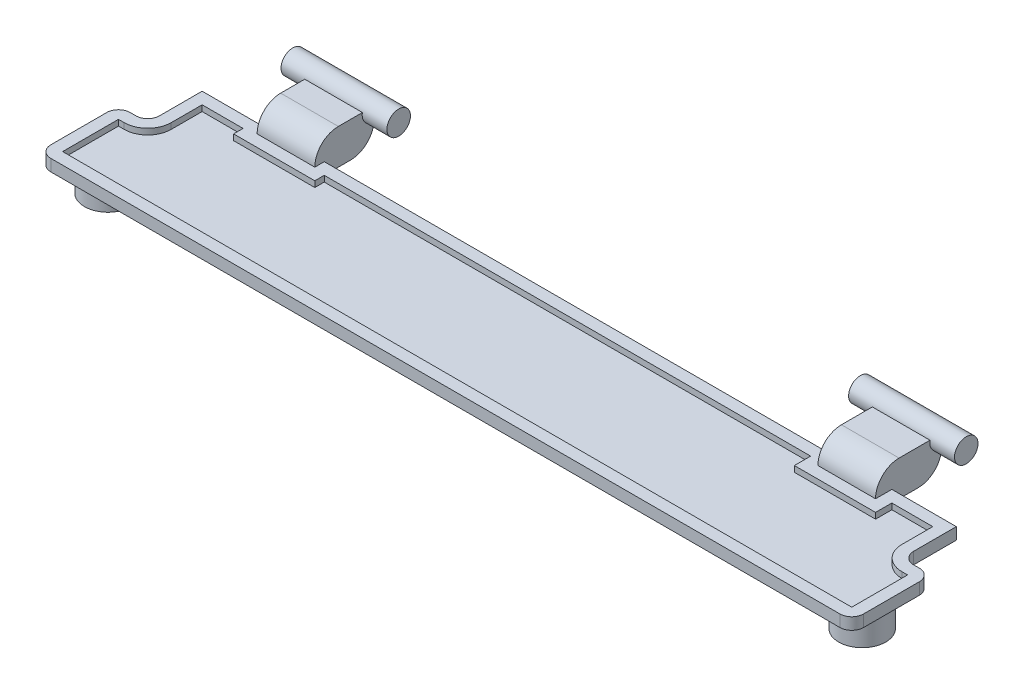
SolidWorks part; units mm, degrees
material "Alloy Steel"
ref_plane "Front Plane" through (0, 0, 0) normal (0, 0, 1) x (1, 0, 0)
ref_plane "Top Plane" through (0, 0, 0) normal (0, 1, 0) x (1, 0, 0)
ref_plane "Right Plane" through (0, 0, 0) normal (1, 0, 0) x (0, 0, -1)
sketch "Sketch1" plane through (0, 0, 0) normal (0, 1, 0) x (1, 0, 0)
  line L0 (0, 0) -> (64.1, 0) construction
  circle A0 centre (64.1, 0) radius 2
  circle A1 centre (0, 0) radius 2
extrude "Boss-Extrude1" add sketch "Sketch1" along normal blind 2.5
sketch "Sketch2" plane through (0, 2.5, 0) normal (0, 1, 0) x (1, 0, 0)
  line L3 (0, 3.3731) -> (0, 8)
  line L4 (0, 8) -> (64.1, 8)
  line L5 (64.1, 3.3731) -> (64.1, 8)
  line L6 (66.5854, -3.3731) -> (-2.4854, -3.3731)
  line L7 (66.5854, -3.3731) -> (66.5854, 3.3731)
  line L8 (66.5854, 3.3731) -> (64.1, 3.3731)
  line L9 (-2.4854, -3.3731) -> (-2.4854, 3.3731)
  line L12 (0, 3.3731) -> (-2.4854, 3.3731)
  point P4 (32.05, 0)
  point P7 (32.05, 0)
extrude "Boss-Extrude3" add sketch "Sketch2" along normal blind 1
fillet "Fillet1" radius 1 6 edges at (0, 3, -3.3731) (64.1, 3, -3.3731) (66.5854, 3, -3.3731) (66.5854, 3, 3.3731) (-2.4854, 3, 3.3731) (-2.4854, 3, -3.3731)
sketch "Sketch3" plane through (0, 3.5, 0) normal (0, 1, 0) x (1, 0, 0)
  line L0 (32.05, 8) -> (3.43, 8) construction
  line L1 (64.1, 8) -> (0, 8) construction
  line L2 (32.05, 8) -> (60.67, 8) construction
  line L3 (3.43, 8) -> (3.43, 12.2253) construction
  line L4 (3.43, 12.2253) -> (12.43, 12.2253) construction
  line L5 (60.67, 8) -> (60.67, 12.2253) construction
  line L6 (60.67, 12.2253) -> (51.67, 12.2253) construction
  line L7 (7.93, 12.2253) -> (7.93, 7.1953) construction
  line L8 (56.17, 12.2253) -> (56.17, 6.616) construction
  line L9 (12.43, 12.2253) -> (50.1115, 12.2253) construction
  line L10 (5.48, 7.1953) -> (10.38, 7.1953)
  line L11 (5.48, 7.1953) -> (5.48, 12.2253)
  line L12 (5.48, 12.2253) -> (10.38, 12.2253)
  line L13 (10.38, 7.1953) -> (10.38, 12.2253)
  line L14 (5.48, 7.1953) -> (10.38, 12.2253) construction
  line L15 (5.48, 12.2253) -> (10.38, 7.1953) construction
  line L16 (58.62, 6.616) -> (53.72, 6.616)
  line L17 (58.62, 6.616) -> (58.62, 12.2253)
  line L18 (58.62, 12.2253) -> (53.72, 12.2253)
  line L19 (53.72, 6.616) -> (53.72, 12.2253)
  line L20 (58.62, 6.616) -> (53.72, 12.2253) construction
  line L21 (58.62, 12.2253) -> (53.72, 6.616) construction
  point P13 (7.93, 9.7103)
  point P18 (56.17, 9.4207)
  dimension "D1" = 28.62
extrude "Boss-Extrude4" add sketch "Sketch3" along normal blind 2 and the other way blind 1
sketch "Sketch4" plane through (5.48, 0, 0) normal (-1, 0, 0) x (0, 0, 1)
  line L0 (-12.2253, 2.5) -> (-12.2253, 5.5) construction
  circle A0 centre (-12.2253, 5.3165) radius 1
extrude "Boss-Extrude5" add sketch "Sketch4" along normal blind 2 and the other way blind 7
sketch "Sketch5" plane through (53.72, 0, 0) normal (-1, 0, 0) x (0, 0, 1)
  circle A0 centre (-12.2253, 5.3165) radius 1
extrude "Boss-Extrude6" add sketch "Sketch5" along normal blind 2 and the other way blind 7
fillet "Fillet2" radius 2 2 edges at (56.17, 5.5, -6.616) (7.93, 5.5, -7.1953)
fillet "Fillet3" radius 2 1 edges at (56.17, 2.5, -12.2253)
sketch "Sketch6" plane through (0, 3.5, 0) normal (0, 1, 0) x (1, 0, 0)
  line L32 (59.62, 5.616) -> (52.72, 5.616)
  line L33 (52.72, 5.616) -> (52.72, 7)
  line L34 (52.72, 7) -> (11.38, 7)
  line L35 (11.38, 7) -> (11.38, 6.1953)
  line L36 (59.62, 5.616) -> (52.72, 5.616)
  line L37 (4.48, 6.1953) -> (4.48, 7)
  line L38 (4.48, 7) -> (1, 7)
  line L39 (1, 7) -> (1, 4.3731)
  line L40 (-1, 2.3731) -> (-1.4854, 2.3731)
  line L41 (-1.4854, 2.3731) -> (-1.4854, -2.3731)
  line L42 (-1.4854, -2.3731) -> (65.5854, -2.3731)
  line L43 (65.5854, -2.3731) -> (65.5854, 2.3731)
  line L44 (65.5854, 2.3731) -> (65.1, 2.3731)
  line L45 (63.1, 4.3731) -> (63.1, 7)
  line L46 (63.1, 7) -> (59.62, 7)
  line L47 (59.62, 7) -> (59.62, 5.616)
  line L48 (11.38, 6.1953) -> (4.48, 6.1953)
  line L49 (52.72, 5.616) -> (52.72, 7)
  line L50 (52.72, 7) -> (11.38, 7)
  line L51 (11.38, 7) -> (11.38, 6.1953)
  line L52 (11.38, 6.1953) -> (4.48, 6.1953)
  line L53 (4.48, 6.1953) -> (4.48, 7)
  line L54 (4.48, 7) -> (1, 7)
  line L55 (1, 7) -> (1, 4.3731)
  line L56 (-1, 2.3731) -> (-1.4854, 2.3731)
  line L57 (-1.4854, 2.3731) -> (-1.4854, -2.3731)
  line L58 (-1.4854, -2.3731) -> (65.5854, -2.3731)
  line L59 (65.5854, -2.3731) -> (65.5854, 2.3731)
  line L60 (65.5854, 2.3731) -> (65.1, 2.3731)
  line L61 (63.1, 4.3731) -> (63.1, 7)
  line L62 (63.1, 7) -> (59.62, 7)
  line L63 (59.62, 7) -> (59.62, 5.616)
  arc A12 (-1, 2.3731) -> (1, 4.3731) centre (-1, 4.3731) ccw
  arc A13 (63.1, 4.3731) -> (65.1, 2.3731) centre (65.1, 4.3731) ccw
  arc A14 (-1, 2.3731) -> (1, 4.3731) centre (-1, 4.3731) ccw
  arc A15 (63.1, 4.3731) -> (65.1, 2.3731) centre (65.1, 4.3731) ccw
  dimension "D1" = 1
extrude "Cut-Extrude1" cut sketch "Sketch6" against normal blind 0.5
fillet "Fillet4" radius 2 1 edges at (7.93, 2.5, -12.2253)
equation "\"2.1.00mm\"=3"
